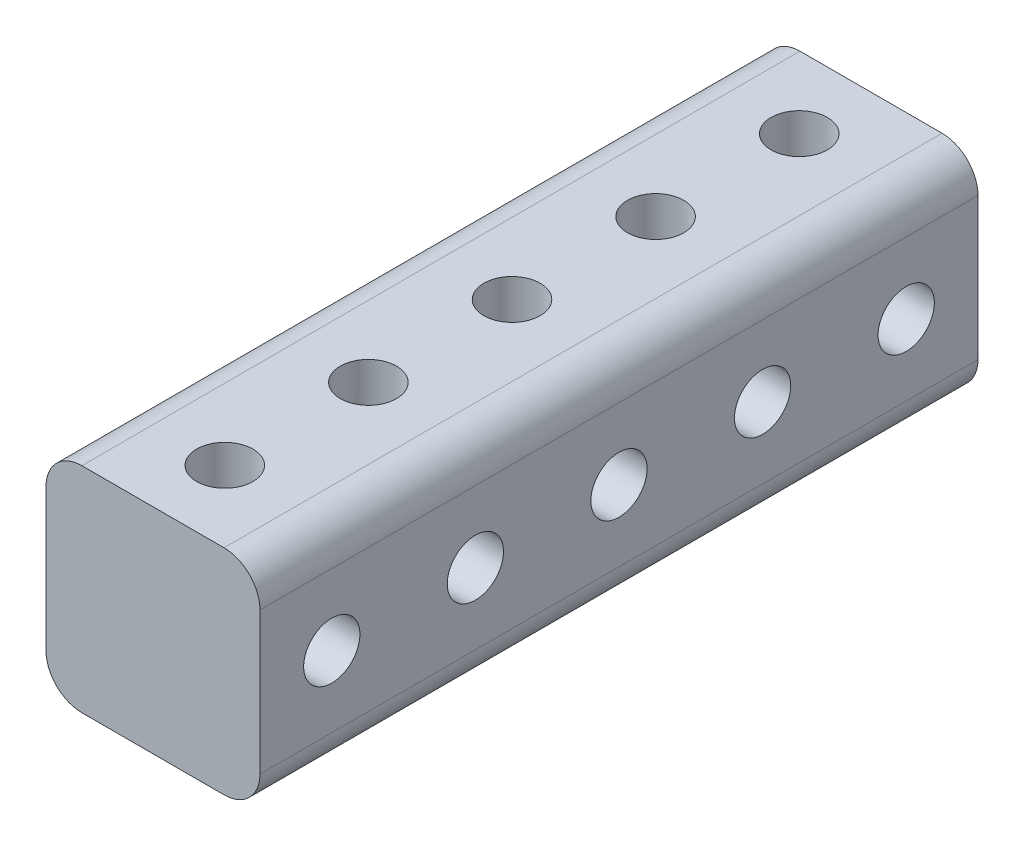
SolidWorks part; units mm, degrees
material "PET"
ref_plane "Front Plane" through (0, 0, 0) normal (0, 0, 1) x (1, 0, 0)
ref_plane "Top Plane" through (0, 0, 0) normal (0, 1, 0) x (1, 0, 0)
ref_plane "Right Plane" through (0, 0, 0) normal (1, 0, 0) x (0, 0, -1)
sketch "Sketch1" plane through (0, 0, 0) normal (0, 0, 1) x (1, 0, 0)
  line L1 (0, 0) -> (18.923, 0)
  line L2 (0, 0) -> (0, 18.923)
  line L3 (0, 18.923) -> (18.923, 18.923)
  line L4 (18.923, 0) -> (18.923, 18.923)
  dimension "D1" = 18.923
extrude "Boss-Extrude1" add sketch "Sketch1" along normal blind 63.5
fillet "Fillet1" radius 3.175 4 edges at (0, 18.923, 31.75) (18.923, 0, 31.75) (0, 0, 31.75) (18.923, 18.923, 31.75)
sketch "Sketch2" plane through (0, 18.923, 0) normal (0, 1, 0) x (1, 0, 0)
  line L0 (15.748, 0) -> (3.175, 0) construction
  line L2 (9.4615, 0) -> (9.4615, -63.5) construction
  line L3 (15.748, -63.5) -> (3.175, -63.5) construction
  circle A0 centre (9.4615, -6.35) radius 2.4892
  circle A1 centre (9.4615, -19.05) radius 2.4892
  circle A2 centre (9.4615, -31.75) radius 2.4892
  circle A3 centre (9.4615, -44.45) radius 2.4892
  circle A4 centre (9.4615, -57.15) radius 2.4892
  point P16 (9.525, -57.2263)
  point P17 (9.525, -19.1263)
  dimension "D1" = 4.9784
  dimension "D4" = 12.7
  dimension "D2" = 6.35
  dimension "D3" = 5
extrude "Cut-Extrude1" cut sketch "Sketch2" against normal blind 63.5
sketch "Sketch3" plane through (18.923, 0, 0) normal (1, 0, 0) x (0, 0, -1)
  line L0 (-63.5, 3.175) -> (-63.5, 15.748) construction
  line L1 (-63.5, 9.4615) -> (0, 9.4615) construction
  line L2 (0, 3.175) -> (0, 15.748) construction
  circle A0 centre (-57.15, 9.4615) radius 2.4892
  circle A1 centre (-44.45, 9.4615) radius 2.4892
  circle A2 centre (-31.75, 9.4615) radius 2.4892
  circle A3 centre (-19.05, 9.4615) radius 2.4892
  circle A4 centre (-6.35, 9.4615) radius 2.4892
  dimension "D2" = 4.9784
  dimension "D4" = 12.7
  dimension "D1" = 6.35
  dimension "D3" = 5
extrude "Cut-Extrude2" cut sketch "Sketch3" against normal blind 63.5
